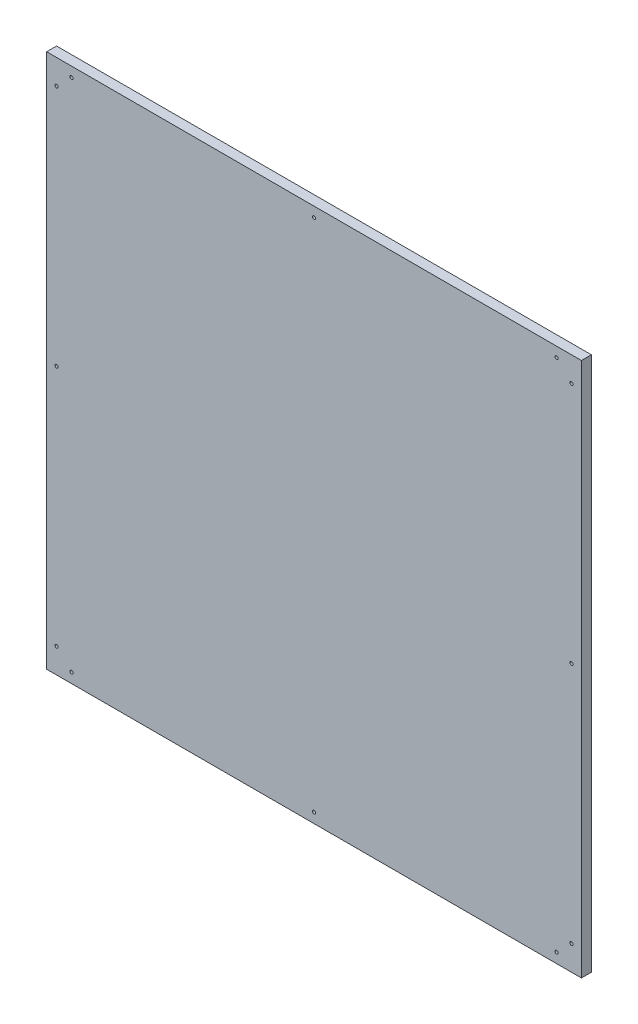
SolidWorks part; units mm, degrees
material "PE High Density Film"
ref_plane "Front Plane" through (0, 0, 0) normal (0, 0, 1) x (1, 0, 0)
ref_plane "Top Plane" through (0, 0, 0) normal (0, 1, 0) x (1, 0, 0)
ref_plane "Right Plane" through (0, 0, 0) normal (1, 0, 0) x (0, 0, -1)
sketch "Sketch1" plane through (0, 0, 0) normal (0, 0, 1) x (1, 0, 0)
  line L1 (0, 0) -> (683.26, 0)
  line L2 (0, 0) -> (0, 683.26)
  line L3 (0, 683.26) -> (683.26, 683.26)
  line L4 (683.26, 0) -> (683.26, 683.26)
  dimension "D1" = 683.26
extrude "Boss-Extrude1" add sketch "Sketch1" along normal blind 12.7
sketch "Sketch6" plane through (0, 0, 12.7) normal (0, 0, 1) x (1, 0, 0)
  line L0 (683.26, 683.26) -> (0, 683.26) construction
  line L1 (0, 683.26) -> (0, 0) construction
  line L2 (0, 0) -> (683.26, 683.26) construction
  line L3 (683.26, 683.26) -> (341.63, 341.63) construction
  line L4 (341.63, 341.63) -> (341.63, 683.26) construction
  line L6 (341.63, 341.63) -> (0, 341.63) construction
  point P0 (31.75, 670.56)
  point P5 (12.7, 651.51)
  point P20 (670.56, 651.51)
  point P21 (651.51, 670.56)
  point P22 (670.56, 31.75)
  point P23 (651.51, 12.7)
  point P24 (31.75, 12.7)
  point P25 (12.7, 31.75)
  point P26 (341.63, 670.56)
  point P29 (12.7, 341.63)
  point P32 (670.56, 341.63)
  point P33 (341.63, 12.7)
  dimension "D1" = 12.7
  dimension "D2" = 31.75
  dimension "D3" = 31.75
  dimension "D4" = 12.7
  dimension "D5" = 12.7
  dimension "D6" = 12.7
  dimension "D7" = 309.88
hole_wizard "#10-32 Tapped Hole1" positions "Sketch6" profile "Sketch7" tap size "#10-32" standard "ANSI Inch" end condition through all
sketch "Sketch7" plane through (31.75, 670.56, 12.7) normal (1, 0, 0) x (0, -1, 0)
  line L0 (0, 0) -> (0, 12.7)
  line L1 (0, 12.7) -> (2.0193, 12.7)
  line L2 (2.0193, 12.7) -> (2.0193, 0)
  line L5 (2.0193, 0) -> (0, 0)
  line L11 (0, -6.35) -> (0, 107.95) construction
  dimension "Thru Tap Drill Dia." = 4.0386
  dimension "Thru Tap Drill Depth" = 12.7
cosmetic thread "Hole Thread1" parameters "D2"=4.826
cosmetic thread "Hole Thread2" parameters "D2"=4.826
cosmetic thread "Hole Thread3" parameters "D2"=4.826
cosmetic thread "Hole Thread4" parameters "D2"=4.826
cosmetic thread "Hole Thread5" parameters "D2"=4.826
cosmetic thread "Hole Thread6" parameters "D2"=4.826
cosmetic thread "Hole Thread7" parameters "D2"=4.826
cosmetic thread "Hole Thread8" parameters "D2"=4.826
cosmetic thread "Hole Thread9" parameters "D2"=4.826
cosmetic thread "Hole Thread10" parameters "D2"=4.826
cosmetic thread "Hole Thread11" parameters "D2"=4.826
cosmetic thread "Hole Thread12" parameters "D2"=4.826
